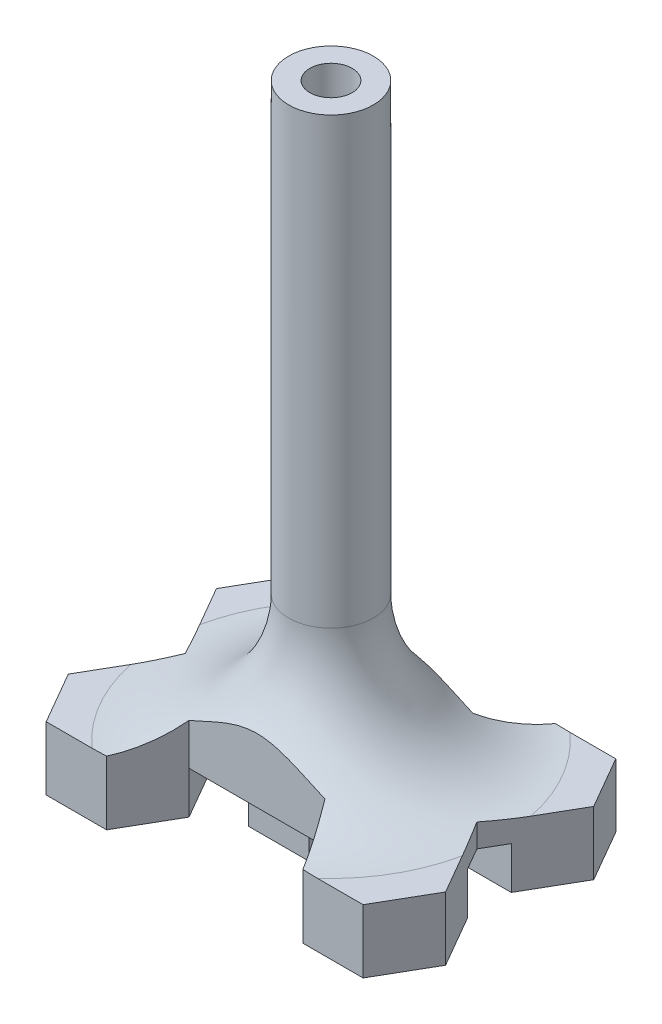
SolidWorks part; units mm, degrees
ref_plane "Alzado" through (0, 0, 0) normal (0, 0, 1) x (1, 0, 0)
ref_plane "Planta" through (0, 0, 0) normal (0, 1, 0) x (1, 0, 0)
ref_plane "Vista lateral" through (0, 0, 0) normal (1, 0, 0) x (0, 0, -1)
sketch "Croquis1" plane through (0, 0, 0) normal (0, 1, 0) x (1, 0, 0)
  circle A0 centre (0, 0) radius 10
  dimension "D1" = 20
extrude "Saliente-Extruir1" add sketch "Croquis1" along normal blind 150
sketch "Croquis2" plane through (0, 0, 0) normal (0, -1, 0) x (1, 0, 0)
  line L1 (14.2606, 0) -> (7.1303, 12.35)
  line L2 (7.1303, 12.35) -> (-7.1303, 12.35)
  line L3 (-7.1303, 12.35) -> (-14.2606, 0)
  line L4 (-14.2606, 0) -> (-7.1303, -12.35)
  line L5 (-7.1303, -12.35) -> (7.1303, -12.35)
  line L6 (7.1303, -12.35) -> (14.2606, 0)
  line L24 (26.9279, 0) -> (-26.9279, 0) construction
  line L25 (-16.0503, -17.5) -> (-23.1806, -5.15)
  line L26 (-16.0503, 17.5) -> (-23.1806, 29.85)
  line L27 (-23.1806, 29.85) -> (-37.4412, 29.85)
  line L28 (-37.4412, 29.85) -> (-44.5714, 17.5)
  line L29 (-44.5714, 17.5) -> (-37.4412, 5.15)
  line L30 (-37.4412, 5.15) -> (-23.1806, 5.15)
  line L31 (-23.1806, 5.15) -> (-16.0503, 17.5)
  line L32 (-23.1806, -5.15) -> (-37.4412, -5.15)
  line L33 (-37.4412, -5.15) -> (-44.5714, -17.5)
  line L34 (-44.5714, -17.5) -> (-37.4412, -29.85)
  line L35 (-37.4412, -29.85) -> (-23.1806, -29.85)
  line L36 (-23.1806, -29.85) -> (-16.0503, -17.5)
  line L37 (44.5714, 17.5) -> (37.4412, 29.85)
  line L38 (37.4412, 29.85) -> (23.1806, 29.85)
  line L39 (23.1806, 29.85) -> (16.0503, 17.5)
  line L40 (16.0503, 17.5) -> (23.1806, 5.15)
  line L41 (23.1806, 5.15) -> (37.4412, 5.15)
  line L42 (37.4412, 5.15) -> (44.5714, 17.5)
  line L43 (44.5714, -17.5) -> (37.4412, -5.15)
  line L44 (37.4412, -5.15) -> (23.1806, -5.15)
  line L45 (23.1806, -5.15) -> (16.0503, -17.5)
  line L46 (16.0503, -17.5) -> (23.1806, -29.85)
  line L47 (23.1806, -29.85) -> (37.4412, -29.85)
  line L48 (37.4412, -29.85) -> (44.5714, -17.5)
  line L49 (-37.4412, 29.85) -> (-23.1806, 5.15) construction
  line L50 (-37.4412, -5.15) -> (-23.1806, -29.85) construction
  line L51 (23.1806, -5.15) -> (37.4412, -29.85) construction
  line L52 (23.1806, 29.85) -> (37.4412, 5.15) construction
  circle A1 centre (0, 0) radius 12.35 construction
  circle A2 centre (-30.3109, 17.5) radius 12.35 construction
  circle A3 centre (-30.3109, 17.5) radius 1.75
  circle A4 centre (-30.3109, -17.5) radius 1.75
  circle A5 centre (0, 0) radius 1.75
  circle A6 centre (30.3109, -17.5) radius 1.75
  circle A7 centre (30.3109, 17.5) radius 1.75
  point P13 (0, 0)
  point P47 (30.3109, -17.5)
  point P48 (-30.3109, -17.5)
  point P49 (30.3109, 17.5)
  dimension "D1" = 24.7
  dimension "D8" = 3.5
  dimension "D3" = 10.3
  dimension "D2" = 24.7
  dimension "D4" = 5.15
  dimension "D6" = 2
  dimension "D7" = 10.3
  dimension "D9" = 10.3
  dimension "D5" = 2
extrude "Saliente-Extruir2" add sketch "Croquis2" against normal blind 15 contours A5 | L1 L2 L3 L4 L5 L6 | L25 L32 L33 L34 L35 L36 | A4 | L26 L27 L28 L29 L30 L31 | A3 | A7 | L37 L38 L39 L40 L41 L42 | A6 | L43 L44 L45 L46 L47 L48
sketch "Croquis4" plane through (0, 15, 0) normal (0, 1, 0) x (1, 0, 0)
  line L0 (-44.5714, 17.5) -> (-34.4678, 0)
  line L1 (-34.4678, 0) -> (-44.5714, -17.5)
  line L4 (-44.5714, -17.5) -> (-37.4412, -29.85)
  line L5 (-37.4412, -29.85) -> (-23.1806, -29.85)
  line L6 (-23.1806, -29.85) -> (-16.0503, -17.5)
  line L7 (-16.0503, -17.5) -> (16.0503, -17.5)
  line L8 (-44.5714, 17.5) -> (-37.4412, 29.85)
  line L9 (-37.4412, 29.85) -> (-23.1806, 29.85)
  line L11 (44.5714, 17.5) -> (37.4412, 29.85)
  line L12 (44.5714, 17.5) -> (34.4678, 0)
  line L13 (34.4678, 0) -> (44.5714, -17.5)
  line L14 (44.5714, -17.5) -> (37.4412, -29.85)
  line L15 (37.4412, -29.85) -> (23.1806, -29.85)
  line L16 (23.1806, -29.85) -> (16.0503, -17.5)
  line L17 (-23.1806, 29.85) -> (-16.0503, 17.5)
  line L18 (-16.0503, 17.5) -> (16.0503, 17.5)
  line L19 (16.0503, 17.5) -> (23.1806, 29.85)
  line L20 (23.1806, 29.85) -> (37.4412, 29.85)
  line L21 (-44.5714, 17.5) -> (-37.4412, 29.85) construction
  line L22 (-37.4412, 5.15) -> (-44.5714, 17.5) construction
  line L23 (-37.4412, 29.85) -> (-23.1806, 29.85) construction
  line L24 (-23.1806, 29.85) -> (-16.0503, 17.5) construction
  line L25 (-44.5714, -17.5) -> (-37.4412, -5.15) construction
  line L26 (-37.4412, -29.85) -> (-44.5714, -17.5) construction
  line L27 (-23.1806, -29.85) -> (-37.4412, -29.85) construction
  line L28 (-16.0503, -17.5) -> (-23.1806, -29.85) construction
  line L29 (23.1806, -29.85) -> (16.0503, -17.5) construction
  line L30 (37.4412, -29.85) -> (23.1806, -29.85) construction
  line L31 (44.5714, -17.5) -> (37.4412, -29.85) construction
  line L32 (37.4412, -5.15) -> (44.5714, -17.5) construction
  line L33 (44.5714, 17.5) -> (37.4412, 5.15) construction
  line L34 (37.4412, 29.85) -> (44.5714, 17.5) construction
  line L35 (16.0503, 17.5) -> (23.1806, 29.85) construction
extrude "Saliente-Extruir4" add sketch "Croquis4" against normal blind 5
fillet "Redondeo1" radius 30 1 edges at (0, 15, -10)
sketch "Croquis5" plane through (0, 0, 0) normal (0, -1, 0) x (1, 0, 0)
  circle A0 centre (0, 0) radius 5
  dimension "D1" = 10
extrude "Cortar-Extruir1" cut sketch "Croquis5" against normal through all
